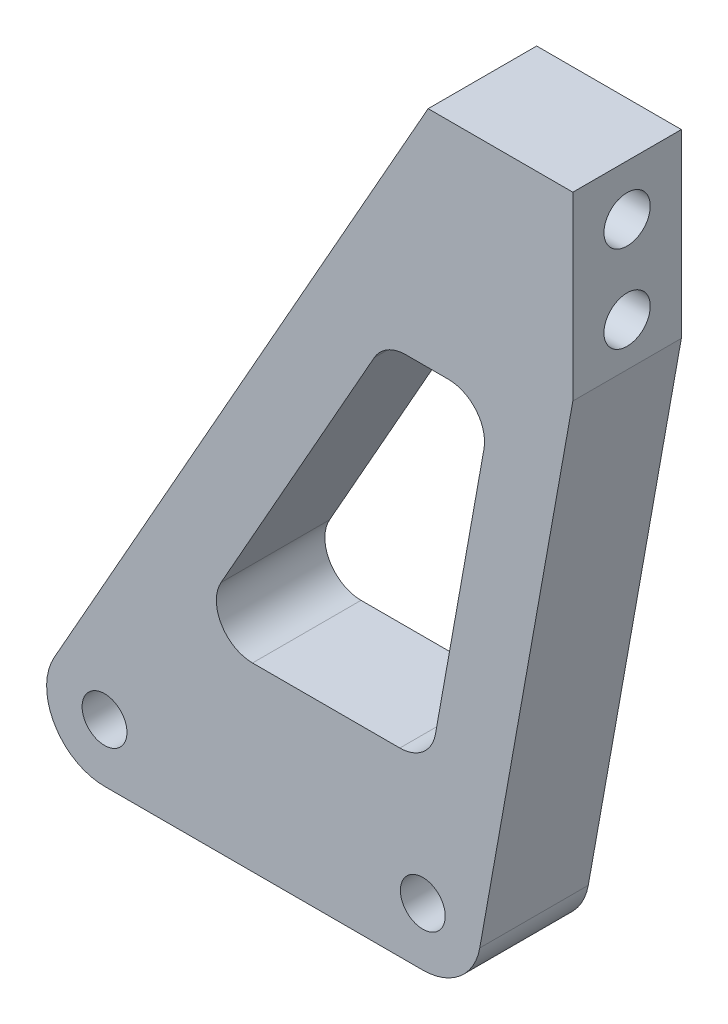
SolidWorks part; units mm, degrees
ref_plane "Front Plane" through (0, 0, 0) normal (0, 0, 1) x (1, 0, 0)
ref_plane "Top Plane" through (0, 0, 0) normal (0, 1, 0) x (1, 0, 0)
ref_plane "Right Plane" through (0, 0, 0) normal (1, 0, 0) x (0, 0, -1)
sketch "Sketch1" plane through (0, 0, 0) normal (0, 0, 1) x (1, 0, 0)
  line L0 (-11, 0) -> (11, 0) construction
  line L1 (-11, 4) -> (11, 4)
  line L2 (-11, -4) -> (11, -4)
  arc A0 (-11, 4) -> (-11, -4) centre (-11, 0) ccw
  arc A1 (11, -4) -> (11, 4) centre (11, 0) ccw
  point P2 (0, 0)
  dimension "D1" = 8
extrude "Boss-Extrude1" add sketch "Sketch1" along normal blind 7.5 contours A1 L1 A0 L2 | A1 A0 L1 region at (0, 0, 0)
sketch "Sketch2" plane through (0, 0, 7.5) normal (0, 0, 1) x (1, 0, 0)
  circle A0 centre (-11, 0) radius 1.55
  arc A2 (-11, 4) -> (-11, -4) centre (-11, 0) ccw construction
  dimension "D1" = 3.1
extrude "Cut-Extrude1" cut sketch "Sketch2" against normal through all
mirror "Mirror1" about plane through (0, 0, 0) normal (1, 0, 0) of "Cut-Extrude1"
sketch "Sketch12" plane through (0, 0, 7.5) normal (0, 0, 1) x (1, 0, 0)
  line L0 (11, 0) -> (21.37, 0) construction
  line L1 (21.37, 0) -> (21.37, 47.75) construction
  line L2 (21.37, 47.75) -> (11.37, 47.75)
  line L3 (11.37, 47.75) -> (-14.483, 1.9668)
  line L4 (21.37, 47.75) -> (21.37, 35.25)
  line L5 (21.37, 35.25) -> (14.9375, -0.7044)
  line L6 (-11, 4) -> (11, 4) construction
  line L7 (-11, 4) -> (11, 4)
  arc A0 (11, -4) -> (11, 4) centre (11, 0) ccw
  arc A1 (-11, 4) -> (-11, -4) centre (-11, 0) ccw construction
  arc A2 (11, -4) -> (11, 4) centre (11, 0) ccw construction
  arc A3 (-11, 4) -> (-11, -4) centre (-11, 0) ccw
  arc M8 (11, -4) -> (11, 4) centre (11, 0) ccw
  line M9 (11, 4) -> (-11, 4)
  arc M10 (-11, 4) -> (-11, -4) centre (-11, 0) ccw
  dimension "D1" = 10.37
  dimension "D2" = 47.75
  dimension "D3" = 10
  dimension "D4" = 12.5
extrude "Boss-Extrude6" add sketch "Sketch12" against normal up to surface (7.5 mm away) contours L5 L4 L2 L3 M10 M9 M8 region at (8.0471, 22.4429, 7.5) up to face at (9.45, 0, 0)
sketch "Sketch13" plane through (21.37, 0, 0) normal (1, 0, 0) x (0, 0, -1)
  circle A0 centre (-3.75, 38.25) radius 1.6 construction
  circle A1 centre (-3.75, 44.25) radius 1.6 construction
  circle A2 centre (-3.75, 38.25) radius 1.6
  circle A3 centre (-3.75, 44.25) radius 1.6
extrude "Cut-Extrude2" cut sketch "Sketch13" against normal up to surface (15.3645 mm away) up to face at (-1.5565, 24.8584, 3.75)
sketch "Sketch15" plane through (0, 0, 7.5) normal (0, 0, 1) x (1, 0, 0)
  line L0 (11.37, 47.75) -> (-14.483, 1.9668) construction
  line L6 (15.7539, 32.25) -> (8.3595, 32.25)
  line L7 (-5.0518, 8.5) -> (11.5048, 8.5)
  line L8 (15.7539, 32.25) -> (11.5048, 8.5)
  line L9 (8.3595, 32.25) -> (-5.0518, 8.5)
  line L13 (11.37, 47.75) -> (-13.6173, 3.5) construction
  line L14 (20.6757, 31.3694) -> (15.6897, 3.5) construction
  line L15 (21.37, 35.25) -> (14.9375, -0.7044) construction
  line L16 (-13.6173, 3.5) -> (15.6897, 3.5) construction
  line L17 (-11, -4) -> (11, -4) construction
  line L18 (15.7238, 45.2915) -> (-5.0518, 8.5) construction
  dimension "D1" = 7.5
  dimension "D3" = 10
  dimension "D4" = 3
  dimension "D2" = 5
extrude "Cut-Extrude8" cut sketch "Sketch15" against normal through all contours L8 L7 L9 L6
fillet "Fillet1" radius 2.5 4 edges at (11.5048, 8.5, 3.75) (15.7539, 32.25, 3.75) (8.3595, 32.25, 3.75) (-5.0518, 8.5, 3.75)
